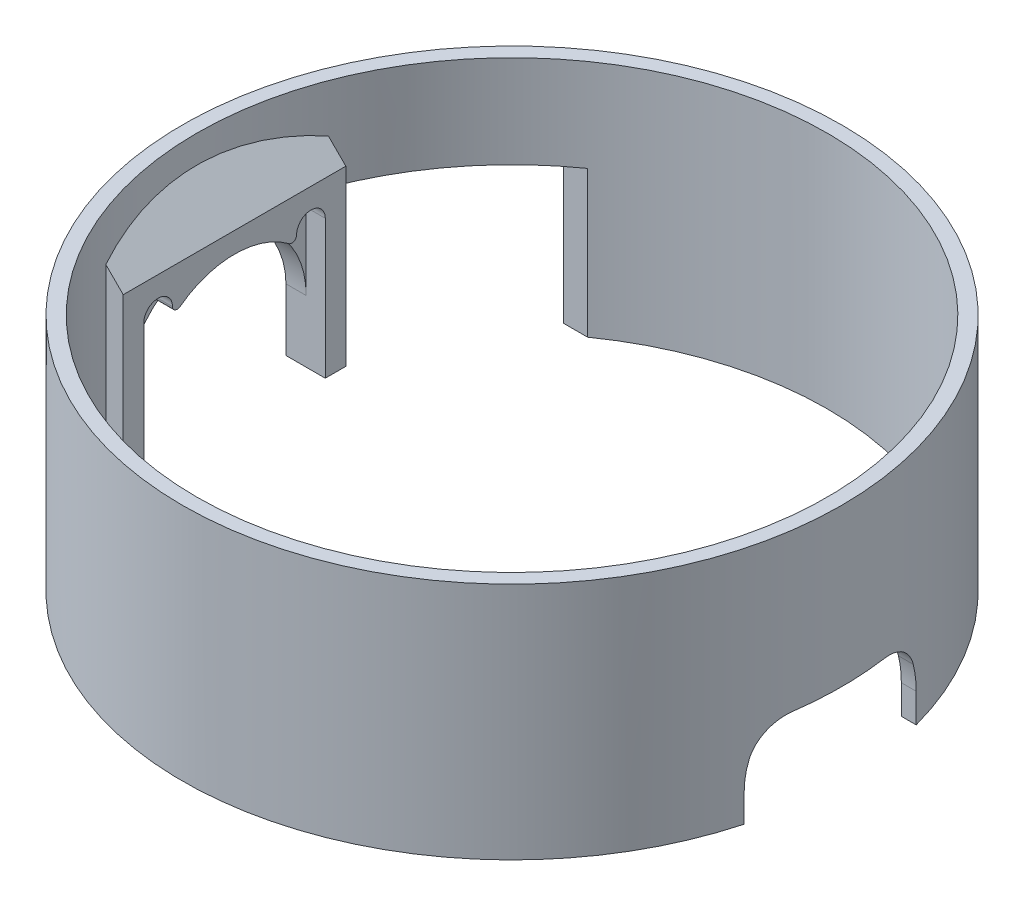
SolidWorks part; units mm, degrees
ref_plane "Front Plane" through (0, 0, 0) normal (0, 0, 1) x (1, 0, 0)
ref_plane "Top Plane" through (0, 0, 0) normal (0, 1, 0) x (1, 0, 0)
ref_plane "Right Plane" through (0, 0, 0) normal (1, 0, 0) x (0, 0, -1)
sketch "Sketch1" plane through (0, 0, 0) normal (0, 1, 0) x (1, 0, 0)
  circle A0 centre (0, 0) radius 69
  circle A1 centre (0, 0) radius 66
  dimension "D1" = 138
  dimension "D2" = 3
extrude "Boss-Extrude1" add sketch "Sketch1" along normal blind 50
sketch "Sketch4" plane through (0, 0, 0) normal (1, 0, 0) x (0, 0, -1)
  line L1 (23.3, 0) -> (53.9, 0)
  line L2 (23.3, 0) -> (23.3, 30.6)
  line L3 (23.3, 30.6) -> (53.9, 30.6)
  line L4 (53.9, 0) -> (53.9, 30.6)
  dimension "D1" = 30.6
  dimension "D2" = 30.6
  dimension "D3" = 0
  dimension "D4" = 23.3
extrude "Cut-Extrude2" cut sketch "Sketch4" against normal through all
sketch "Sketch5" plane through (0, 0, 0) normal (1, 0, 0) x (0, 0, -1)
  line L8 (19, 13) -> (19, -6)
  line L9 (19, -6) -> (-19, -6)
  line L10 (-19, -6) -> (-19, 13)
  arc A1 (19, 13) -> (-19, 13) centre (0, 13) ccw
  dimension "D1" = 19
  dimension "D3" = 13
  dimension "D2" = 19
extrude "Cut-Extrude6" cut sketch "Sketch5" against normal through all
sketch "Sketch6" plane through (0, 0, 0) normal (1, 0, 0) x (0, 0, -1)
  line L0 (19, 13) -> (19, 0)
  line L2 (-19, 0) -> (-19, 13)
  line L3 (23.3, 13) -> (23.3, 0)
  line L4 (-23.3, 0) -> (-23.3, 13)
  line L5 (23.3, 0) -> (19, 0)
  line L6 (-19, 0) -> (-23.3, 0)
  arc A0 (19, 13) -> (-19, 13) centre (0, 13) ccw
  arc A1 (23.3, 13) -> (-23.3, 13) centre (0, 13) ccw
  dimension "D1" = 19
  dimension "D3" = 0
  dimension "D2" = 4.3
extrude "Boss-Extrude2" add sketch "Sketch6" against normal up to next from offset 58.1 offset against normal yes
sketch "Sketch7" plane through (-58.1, 0, 0) normal (1, 0, 0) x (0, 0, -1)
  line L0 (0, 36.3) -> (15, 36.3) construction
  arc A0 (23.3, 13) -> (-23.3, 13) centre (0, 13) ccw construction
  dimension "D1" = 15
ref_plane "Plane2" through (-10.9, -10.9, 0) normal (-0.7071, -0.7071, 0) x (0, 0, -1)
sketch "Sketch8" plane through (-10.9, -10.9, 0) normal (-0.7071, -0.7071, 0) x (0, 0, -1)
  line L0 (23.3, -41.0829) -> (23.3, -50.2753) construction
  line L1 (-23.3, -84.0829) -> (23.3, -84.0829)
  line L2 (-23.3, -84.0829) -> (-23.3, -49.0829)
  line L3 (-23.3, -49.0829) -> (23.3, -49.0829)
  line L4 (23.3, -84.0829) -> (23.3, -49.0829)
  line L5 (-23.3, -50.2753) -> (-23.3, -41.0829) construction
  line L6 (19, -41.0829) -> (23.3, -41.0829) construction
  dimension "D1" = 0
  dimension "D2" = 0
  dimension "D3" = 8
  dimension "D4" = 35
extrude "Boss-Extrude4" add sketch "Sketch8" along normal blind 30 contours L2 L1 L4 L3
sketch "Sketch9" plane through (0, 0, 0) normal (0, -1, 0) x (1, 0, 0)
  line L0 (-58.1, -23.3) -> (-61.7504, -23.3)
  line L1 (-64.947, -23.3) -> (-58.1, -23.3) construction
  line L6 (-38.0892, -53.9) -> (-43.0789, -53.9)
  line L7 (-38.0892, -53.9) -> (-43.0789, -53.9)
  line L12 (-66.3325, 19) -> (-58.1, 19)
  line L14 (-58.1, 19) -> (-58.1, 23.3)
  line L15 (-58.1, 23.3) -> (-61.7504, 23.3)
  line L18 (-58.1, 19) -> (-58.1, 23.3)
  line L19 (-58.1, 23.3) -> (-61.7504, 23.3)
  line L20 (-58.1, 19) -> (-58.1, -19)
  line L24 (-58.1, -19) -> (-66.3325, -19)
  line L25 (-64.947, -23.3) -> (-58.1, -23.3)
  line L27 (-58.1, -23.3) -> (-58.1, -19)
  line L31 (-58.1, -23.3) -> (-58.1, -19)
  arc A6 (-43.0789, -53.9) -> (-66.3325, 19) centre (0, 0) ccw
  arc A7 (-38.0892, -53.9) -> (-61.7504, 23.3) centre (0, 0) ccw
  arc A8 (-43.0789, -53.9) -> (-66.3325, 19) centre (0, 0) ccw
  arc A9 (-38.0892, -53.9) -> (-61.7504, 23.3) centre (0, 0) ccw
  arc A10 (-66.3325, -19) -> (-66.3325, 19) centre (0, 0) ccw
  arc A11 (-61.7504, -23.3) -> (-61.7504, 23.3) centre (0, 0) ccw
  arc A12 (-66.3325, -19) -> (-64.947, -23.3) centre (0, 0) ccw
  arc A14 (-66.3325, -19) -> (-64.947, -23.3) centre (0, 0) ccw
  circle A16 centre (0, 0) radius 69
  arc A18 (-61.7504, -23.3) -> (-61.7504, 23.3) centre (0, 0) ccw
  line M15 (-66.3325, 19) -> (-58.1, 19)
  line M16 (-58.1, 19) -> (-58.1, 23.3)
  line M17 (-58.1, 23.3) -> (-61.7504, 23.3)
  arc M18 (-61.7504, 23.3) -> (-38.0892, -53.9) centre (0, 0) cw
  dimension "D1" = 0
  dimension "D2" = 0
extrude "Cut-Extrude7" cut sketch "Sketch9" against normal through all flip side to cut contours A16
extrude "Cut-Extrude8" cut sketch "Sketch9<3>" against normal through all contours L31 A11 M15 M18 M17 M16 region at (1.3919, 0, 0)
sketch "Sketch9<3>" plane through (0, 0, 0) normal (0, -1, 0) x (1, 0, 0) same geometry as "Sketch9"
extrude "Cut-Extrude9" cut sketch "Sketch5<2>" against normal through all
sketch "Sketch5<2>" plane through (0, 0, 0) normal (1, 0, 0) x (0, 0, -1) same geometry as "Sketch5"
sketch "Sketch11" plane through (-58.1, 0, 0) normal (1, 0, 0) x (0, 0, -1)
  line L0 (-19, 29) -> (-19, 11)
  line L1 (-19, 0) -> (-19, 13) construction
  line L2 (-19, 11) -> (-13, 11)
  line L3 (-13, 11) -> (-13, 29)
  line L4 (13, 29) -> (13, 11)
  line L5 (19, 29) -> (19, 11)
  line L6 (19, 13) -> (19, 0) construction
  line L7 (13, 11) -> (19, 11)
  arc A0 (19, 29) -> (13, 29) centre (16, 29) ccw
  arc A1 (-13, 29) -> (-19, 29) centre (-16, 29) ccw
  dimension "D1" = 6
  dimension "D2" = 6
  dimension "D3" = 18
  dimension "D4" = 18
extrude "Cut-Extrude11" cut sketch "Sketch11" against normal blind 4
fillet "Fillet3" radius 1 2 edges at (-60.1, 26.8564, -13) (-60.1, 26.8564, 13)
sketch "Sketch12" plane through (0, 0, 0) normal (1, 0, 0) x (0, 0, -1)
  line L39 (-18, -0.9) -> (18, -0.9)
  line L42 (18, -0.9) -> (18, 6.1)
  line L43 (9.5394, 17.1) -> (-9.5394, 17.1)
  line L44 (-18, 6.1) -> (-18, -0.9)
  line L45 (18, -0.9) -> (18, 6.1)
  line L46 (9.5394, 17.1) -> (-9.5394, 17.1)
  line L47 (-18, 6.1) -> (-18, -0.9)
  arc A58 (18, 6.1) -> (17.1709, 11.5) centre (0, 6.1) ccw
  arc A59 (17.1709, 11.5) -> (9.5394, 17.1) centre (9.5394, 9.1) ccw
  arc A60 (-17.1709, 11.5) -> (-18, 6.1) centre (0, 6.1) ccw
  arc A61 (-9.5394, 17.1) -> (-17.1709, 11.5) centre (-9.5394, 9.1) ccw
  arc A62 (18, 6.1) -> (17.1709, 11.5) centre (0, 6.1) ccw
  arc A63 (17.1709, 11.5) -> (9.5394, 17.1) centre (9.5394, 9.1) ccw
  arc A64 (-17.1709, 11.5) -> (-18, 6.1) centre (0, 6.1) ccw
  arc A65 (-9.5394, 17.1) -> (-17.1709, 11.5) centre (-9.5394, 9.1) ccw
  dimension "D1" = 0
extrude "Cut-Extrude12" cut sketch "Sketch12" along normal through all
